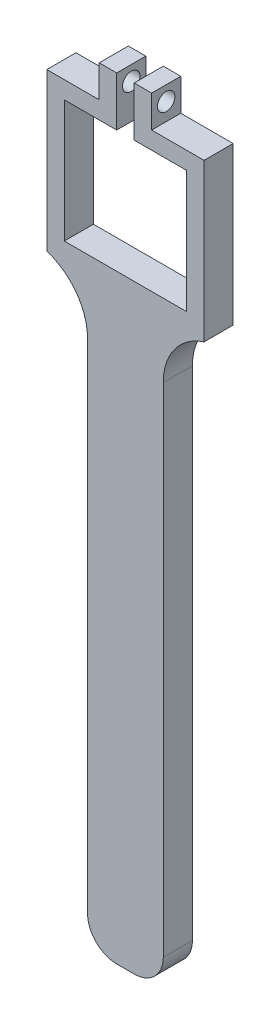
SolidWorks part; units mm, degrees
ref_plane "Front Plane" through (0, 0, 0) normal (0, 0, 1) x (1, 0, 0)
ref_plane "Top Plane" through (0, 0, 0) normal (0, 1, 0) x (1, 0, 0)
ref_plane "Right Plane" through (0, 0, 0) normal (1, 0, 0) x (0, 0, -1)
sketch "Sketch1" plane through (0, 0, 0) normal (0, 0, 1) x (1, 0, 0)
  line L0 (4.6811, -8.6575) -> (11.6811, -8.6575)
  line L1 (-12.3189, 15.3425) -> (-3.3189, 15.3425)
  line L2 (-12.3189, 15.3425) -> (-12.3189, -5.6575)
  line L3 (-12.3189, -5.6575) -> (8.6811, -5.6575)
  line L4 (8.6811, 15.3425) -> (8.6811, -5.6575)
  line L5 (-15.3189, 18.3425) -> (-6.3189, 18.3425)
  line L6 (-15.3189, 18.3425) -> (-15.3189, -8.6575)
  line L7 (-15.3189, -8.6575) -> (-8.3189, -8.6575)
  line L8 (11.6811, 18.3425) -> (11.6811, -8.6575)
  line L9 (-6.3189, 23.8425) -> (-3.3189, 23.8425)
  line L10 (-6.3189, 23.8425) -> (-6.3189, 18.3425)
  line L11 (-0.3189, 15.3425) -> (8.6811, 15.3425)
  line L12 (-3.3189, 23.8425) -> (-3.3189, 18.3425)
  line L13 (-0.3189, 23.8425) -> (2.6811, 23.8425)
  line L14 (-0.3189, 23.8425) -> (-0.3189, 18.3425)
  line L16 (2.6811, 23.8425) -> (2.6811, 18.3425)
  line L17 (2.6811, 18.3425) -> (11.6811, 18.3425)
  line L18 (-8.3189, -8.6575) -> (-8.3189, -108.6575)
  line L20 (-3.3189, 18.3425) -> (-3.3189, 15.3425)
  line L22 (-0.3189, 18.3425) -> (-0.3189, 15.3425)
  line L23 (-8.3189, -108.6575) -> (4.6811, -108.6575)
  line L24 (4.6811, -8.6575) -> (4.6811, -108.6575)
  dimension "D1" = 21
  dimension "D2" = 21
  dimension "D3" = 3
  dimension "D4" = 3
  dimension "D5" = 3
  dimension "D6" = 3
  dimension "D7" = 4
  dimension "D8" = 4
  dimension "D9" = 3
  dimension "D10" = 3
  dimension "D11" = 5.5
  dimension "D12" = 5.5
  dimension "D13" = 100
  dimension "D14" = 3
extrude "Boss-Extrude1" add sketch "Sketch1" along normal blind 5
fillet "Fillet1" radius 10 2 edges at (-8.3189, -8.6575, 2.5) (4.6811, -8.6575, 2.5)
fillet "Fillet2" radius 5 2 edges at (4.6811, -108.6575, 2.5) (-8.3189, -108.6575, 2.5)
sketch "Sketch3" plane through (-6.3189, 0, 0) normal (-1, 0, 0) x (0, 0, 1)
  line L0 (5, 18.3425) -> (0, 18.3425) construction
  circle A0 centre (2.5, 21.3425) radius 1.5
  dimension "D1" = 3
  dimension "D2" = 3
extrude "Cut-Extrude1" cut sketch "Sketch3" against normal blind 15
